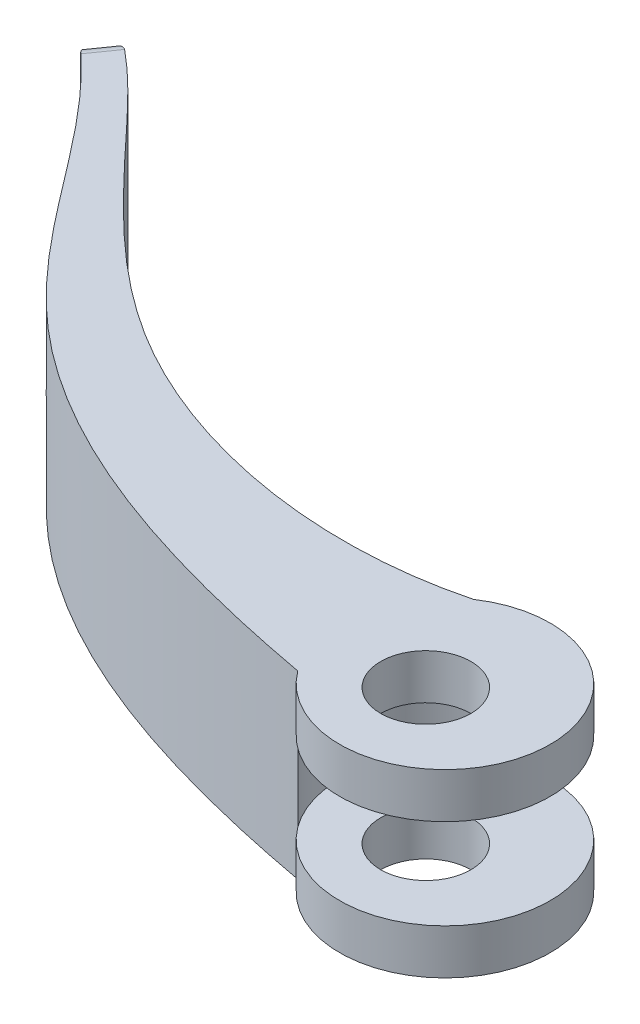
SolidWorks part; units mm, degrees
ref_plane "前视基准面" through (0, 0, 0) normal (0, 0, 1) x (1, 0, 0)
ref_plane "上视基准面" through (0, 0, 0) normal (0, 1, 0) x (1, 0, 0)
ref_plane "右视基准面" through (0, 0, 0) normal (1, 0, 0) x (0, 0, -1)
other "Configuration Table"
sketch "草图1" plane through (0, 0, 0) normal (0, 1, 0) x (1, 0, 0)
  line L0 (-47.9873, 26.482) -> (-49.1369, 24.8454)
  circle A1 centre (0, 0) radius 7
  circle A2 centre (-0.4213, -0.8525) radius 3
  spline S0 degree 3 poles (-3.9086, 5.8071) (-12.38, 3.6056) (-27.3766, 6.3176) (-39.4254, 17.773) (-45.6587, 24.8464) (-47.9873, 26.482) knots 0 0 0 0 0.514096 0.795654 1 1 1 1
  spline S1 degree 3 poles (-49.1369, 24.8454) (-44.8089, 21.0865) (-40.7588, 14.5145) (-28.4427, 1.3629) (-15.6288, -2.308) (-5.6304, -4.1592) knots 0 0 0 0 0.31533 0.428801 1 1 1 1
  point P10 (-0.9702, -1.01)
  point P13 (0, 0)
  point P15 (-0.6561, -1.1272)
  point P17 (-0.4213, -0.8525)
  dimension "D1" = 6
  dimension "15" = 14
  dimension "D3" = 2
extrude "凸台-拉伸1" add sketch "草图1" along normal blind 12 contours L0 S1 A1 S0 region at (-24.2234, 0, -6.687)
extrude "凸台-拉伸2" add sketch "草图1<3>" along normal blind 3 contours A1 region at (3.1963, 0, -6.0042)
sketch "草图1<3>" plane through (0, 0, 0) normal (0, 1, 0) x (1, 0, 0) same geometry as "草图1"
extrude "凸台-拉伸3" add sketch "草图1<4>" against normal blind 3 from surface contours A1 region at (3.1963, 0, -6.0042) starting at face at (-27.1263, 12, -14.377)
sketch "草图1<4>" plane through (0, 0, 0) normal (0, 1, 0) x (1, 0, 0) same geometry as "草图1"
fillet "圆角1" radius 1 4 edges at (-47.9873, 6, -26.482) (-48.5621, 12, -25.6637) (-49.1369, 6, -24.8454) (-48.5621, 0, -25.6637)
